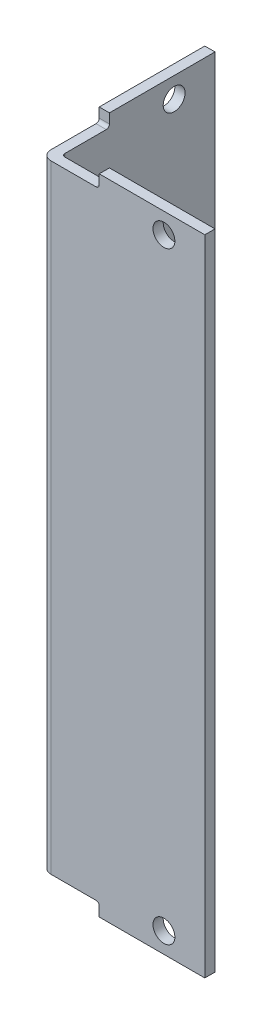
SolidWorks part; units mm, degrees
material "6061-T6 (SS)"
ref_plane "Front Plane" through (0, 0, 0) normal (0, 0, 1) x (1, 0, 0)
ref_plane "Top Plane" through (0, 0, 0) normal (0, 1, 0) x (1, 0, 0)
ref_plane "Right Plane" through (0, 0, 0) normal (1, 0, 0) x (0, 0, -1)
sketch "Sketch1" plane through (0, 0, 0) normal (0, 1, 0) x (1, 0, 0)
  line L1 (-12.7, -12.7) -> (12.7, -12.7)
  line L2 (-12.7, -12.7) -> (-12.7, 12.7)
  line L3 (-12.7, 12.7) -> (12.7, 12.7)
  line L4 (12.7, -12.7) -> (12.7, 12.7)
  line L5 (-12.7, -12.7) -> (12.7, 12.7) construction
  line L6 (-12.7, 12.7) -> (12.7, -12.7) construction
  point P0 (0, 0)
  dimension "D1" = 25.4
  dimension "D2" = 25.4
extrude "Boss-Extrude1" add sketch "Sketch1" along normal mid plane 113.5
sketch "Sketch2" plane through (0, 56.75, 0) normal (0, 1, 0) x (1, 0, 0)
  line L0 (-12.7, 12.7) -> (-12.7, -12.7) construction
  line L1 (12.7, 12.7) -> (-11.1125, 12.7)
  line L2 (12.7, 12.7) -> (12.7, -11.1125)
  line L3 (12.7, -11.1125) -> (-11.1125, -11.1125)
  line L4 (-11.1125, 12.7) -> (-11.1125, -11.1125)
  line L5 (-12.7, -12.7) -> (12.7, -12.7) construction
  dimension "D1" = 1.5875
  dimension "D2" = 1.5875
extrude "Cut-Extrude1" cut sketch "Sketch2" against normal through all
fillet "Fillet1" radius 0.508 1 edges at (-11.1125, 0, 11.1125)
hole_wizard "M3 Clearance Hole1" positions "Sketch3" profile "Sketch4" hole size "M3" standard "ANSI Metric" end condition through all
sketch "Sketch3" plane through (0, 0, 12.7) normal (0, 0, 1) x (1, 0, 0)
  line L1 (-12.7, 56.75) -> (12.7, 56.75) construction
  line L2 (12.7, 56.75) -> (12.7, -56.75) construction
  point P0 (6.35, 47.075)
  dimension "D1" = 6.35
  dimension "D2" = 9.675
sketch "Sketch4" plane through (6.35, 47.075, 12.7) normal (1, 0, 0) x (0, -1, 0)
  line L0 (0, 0) -> (0, 25.4)
  line L1 (0, 25.4) -> (1.7, 25.4)
  line L2 (1.7, 25.4) -> (1.7, 0)
  line L5 (1.7, 0) -> (0, 0)
  line L11 (0, -6.35) -> (0, 107.95) construction
  dimension "Thru Hole Dia." = 3.4
  dimension "Thru Hole Depth" = 25.4
hole_wizard "M3 Clearance Hole2" positions "Sketch5" profile "Sketch6" hole size "M3" standard "ANSI Metric" end condition through all
sketch "Sketch5" plane through (-12.7, 0, 0) normal (-1, 0, 0) x (0, 0, 1)
  line L1 (-12.7, 56.75) -> (12.7, 56.75) construction
  line L2 (-12.7, 56.75) -> (-12.7, -56.75) construction
  point P0 (-6.35, 47.075)
  dimension "D1" = 6.35
  dimension "D2" = 9.675
sketch "Sketch6" plane through (-12.7, 47.075, -6.35) normal (0, 1, 0) x (0, 0, 1)
  line L0 (0, 0) -> (0, 25.4)
  line L1 (0, 25.4) -> (1.7, 25.4)
  line L2 (1.7, 25.4) -> (1.7, 0)
  line L5 (1.7, 0) -> (0, 0)
  line L11 (0, -6.35) -> (0, 107.95) construction
  dimension "Thru Hole Dia." = 3.4
  dimension "Thru Hole Depth" = 25.4
hole_wizard "M3 Clearance Hole3" positions "Sketch7" profile "Sketch8" hole size "M3" standard "ANSI Metric" end condition through all
sketch "Sketch7" plane through (0, 0, 12.7) normal (0, 0, 1) x (1, 0, 0)
  line L2 (-12.7, -56.75) -> (12.7, -56.75) construction
  line L3 (12.7, 56.75) -> (12.7, -56.75) construction
  point P0 (6.35, -46.575)
  dimension "D1" = 6.35
  dimension "D2" = 10.175
sketch "Sketch8" plane through (6.35, -46.575, 12.7) normal (1, 0, 0) x (0, -1, 0)
  line L0 (0, 0) -> (0, 25.4)
  line L1 (0, 25.4) -> (1.7, 25.4)
  line L2 (1.7, 25.4) -> (1.7, 0)
  line L5 (1.7, 0) -> (0, 0)
  line L11 (0, -6.35) -> (0, 107.95) construction
  dimension "Thru Hole Dia." = 3.4
  dimension "Thru Hole Depth" = 25.4
hole_wizard "M3 Clearance Hole4" positions "Sketch9" profile "Sketch10" hole size "M3" standard "ANSI Metric" end condition through all
sketch "Sketch9" plane through (-12.7, 0, 0) normal (-1, 0, 0) x (0, 0, 1)
  line L1 (-12.7, -56.75) -> (12.7, -56.75) construction
  line L2 (-12.7, 56.75) -> (-12.7, -56.75) construction
  point P0 (-6.35, -46.575)
  dimension "D1" = 6.35
  dimension "D2" = 10.175
sketch "Sketch10" plane through (-12.7, -46.575, -6.35) normal (0, 1, 0) x (0, 0, 1)
  line L0 (0, 0) -> (0, 25.4)
  line L1 (0, 25.4) -> (1.7, 25.4)
  line L2 (1.7, 25.4) -> (1.7, 0)
  line L5 (1.7, 0) -> (0, 0)
  line L11 (0, -6.35) -> (0, 107.95) construction
  dimension "Thru Hole Dia." = 3.4
  dimension "Thru Hole Depth" = 25.4
fillet "Fillet2" radius 1.5 1 edges at (-12.7, 0, 12.7)
sketch "Sketch11" plane through (-12.7, 0, 0) normal (-1, 0, 0) x (0, 0, 1)
  line L0 (12.7, 56.75) -> (12.7, -56.75) construction
  line L1 (-12.7, 56.75) -> (4.2, 56.75)
  line L2 (-12.7, 56.75) -> (-12.7, 50.25)
  line L3 (-12.7, 50.25) -> (4.2, 50.25)
  line L4 (4.2, 56.75) -> (4.2, 50.25)
  line L6 (-12.7, -56.75) -> (4.2, -56.75)
  line L7 (-12.7, -56.75) -> (-12.7, -49.75)
  line L8 (-12.7, -49.75) -> (4.2, -49.75)
  line L9 (4.2, -56.75) -> (4.2, -49.75)
  dimension "D1" = 8.5
  dimension "D2" = 6.5
  dimension "D3" = 7
extrude "Cut-Extrude2" cut sketch "Sketch11" against normal up to next
sketch "Sketch12" plane through (0, 0, 12.7) normal (0, 0, 1) x (1, 0, 0)
  line L0 (-12.7, -56.75) -> (-12.7, 56.75) construction
  line L1 (12.7, 56.75) -> (-4.2, 56.75)
  line L2 (12.7, 56.75) -> (12.7, 50.25)
  line L3 (12.7, 50.25) -> (-4.2, 50.25)
  line L4 (-4.2, 56.75) -> (-4.2, 50.25)
  line L5 (12.7, -56.75) -> (-4.2, -56.75)
  line L6 (12.7, -56.75) -> (12.7, -49.75)
  line L7 (12.7, -49.75) -> (-4.2, -49.75)
  line L8 (-4.2, -56.75) -> (-4.2, -49.75)
  dimension "D1" = 8.5
  dimension "D2" = 7
  dimension "D3" = 8.5
  dimension "D4" = 6.5
extrude "Cut-Extrude3" cut sketch "Sketch12" against normal up to next
fillet "Fillet3" radius 3.81 4 edges at (-4.2, -49.75, 11.9062) (-11.9063, -49.75, 4.2) (-11.9063, 50.25, 4.2) (-4.2, 50.25, 11.9062)
sketch "Sketch13" plane through (-12.7, 0, 0) normal (-1, 0, 0) x (0, 0, 1)
  line L0 (4.2, -56.75) -> (4.2, 56.75) construction
  line L9 (2.7, -56.75) -> (2.7, 56.75) construction
  line L10 (-12.7, 50.25) -> (-12.7, -49.75) construction
  line L11 (2.7, -43.4) -> (-12.7, -43.4)
  line L12 (2.7, -43.4) -> (2.7, 43.9)
  line L13 (2.7, 43.9) -> (-12.7, 43.9)
  line L14 (-12.7, -43.4) -> (-12.7, 43.9)
  circle A2 centre (-6.35, 47.075) radius 1.7 construction
  circle A3 centre (-6.35, -46.575) radius 1.7 construction
  dimension "D2" = 3.175
  dimension "D3" = 3.175
  dimension "D1" = 1.5
extrude "Cut-Extrude4" cut sketch "Sketch13" against normal up to next
sketch "Sketch14" plane through (0, 0, 12.7) normal (0, 0, 1) x (1, 0, 0)
  line L0 (-4.2, 56.75) -> (-4.2, -56.75) construction
  line L1 (-2.7, 56.75) -> (-2.7, -56.75) construction
  line L2 (12.7, 50.25) -> (12.7, -49.75) construction
  line L3 (-2.7, -43.4) -> (12.7, -43.4)
  line L4 (-2.7, -43.4) -> (-2.7, 43.9)
  line L5 (-2.7, 43.9) -> (12.7, 43.9)
  line L6 (12.7, -43.4) -> (12.7, 43.9)
  circle A0 centre (6.35, 47.075) radius 1.7 construction
  circle A1 centre (6.35, -46.575) radius 1.7 construction
  dimension "D2" = 3.175
  dimension "D3" = 3.175
  dimension "D1" = 1.5
extrude "Cut-Extrude5" cut sketch "Sketch14" against normal up to next
chamfer "Chamfer2" distance 6.35 angle 45 4 edges at (-11.9063, 43.9, 2.7) (-2.7, 43.9, 11.9062) (-2.7, -43.4, 11.9062) (-11.9062, -43.4, 2.7)
fillet "Fillet5" radius 3.81 8 edges at (3.65, -43.4, 11.9062) (-2.7, -37.05, 11.9062) (-11.9063, -43.4, -3.65) (-11.9063, -37.05, 2.7) (-11.9063, 43.9, -3.65) (-11.9063, 37.55, 2.7) (-2.7, 37.55, 11.9062) (3.65, 43.9, 11.9062)
sketch "Sketch15" plane through (0, 56.75, 0) normal (0, 1, 0) x (1, 0, 0)
  line L0 (-11.2, -12.7) -> (-4.2, -12.7) construction
  line L1 (-12.7, -12.7) -> (-0.39, -12.7)
  line L2 (-12.7, -12.7) -> (-12.7, -0.39)
  line L3 (-12.7, -0.39) -> (-0.39, -0.39)
  line L4 (-0.39, -12.7) -> (-0.39, -0.39)
  line L5 (-12.7, -4.2) -> (-12.7, -11.2) construction
  line L6 (-0.39, -11.1125) -> (-0.39, -12.7) construction
extrude "Cut-Extrude6" cut sketch "Sketch15" against normal up to surface (6.5 mm away) up to face at (6.155, 50.25, 11.9062)
sketch "Sketch16" plane through (0, 50.25, 0) normal (0, 1, 0) x (1, 0, 0)
  line L0 (-11.2, -12.7) -> (12.7, -12.7) construction
  line L1 (-12.7, -12.7) -> (-5.7, -12.7)
  line L2 (-12.7, -12.7) -> (-12.7, -5.7)
  line L3 (-12.7, -5.7) -> (-5.7, -5.7)
  line L4 (-5.7, -12.7) -> (-5.7, -5.7)
  line L5 (-12.7, 12.7) -> (-12.7, -11.2) construction
  dimension "D1" = 7
  dimension "D2" = 7
sketch "Sketch17" plane through (0, -56.75, 0) normal (0, -1, 0) x (1, 0, 0)
  line L0 (-11.2, 12.7) -> (-4.2, 12.7) construction
  line L1 (-12.7, 12.7) -> (-0.39, 12.7)
  line L2 (-12.7, 12.7) -> (-12.7, 0.39)
  line L3 (-12.7, 0.39) -> (-0.39, 0.39)
  line L4 (-0.39, 12.7) -> (-0.39, 0.39)
  line L5 (-12.7, 4.2) -> (-12.7, 11.2) construction
  line L6 (-11.1125, 0.39) -> (-12.7, 0.39) construction
  line L7 (-0.39, 12.7) -> (-0.39, 11.1125) construction
extrude "Cut-Extrude8" cut sketch "Sketch17" against normal up to surface (7 mm away) up to face at (6.155, -49.75, 11.9062)
sketch "Sketch18" plane through (-12.7, 0, 0) normal (-1, 0, 0) x (0, 0, 1)
  line L0 (-12.7, -43.4) -> (-5.2282, -43.4) construction
  line L1 (5.7, -43.4) -> (11.2, -43.4)
  line L2 (5.7, -43.4) -> (5.7, -40.4)
  line L3 (5.7, -40.4) -> (11.2, -40.4)
  line L4 (11.2, -43.4) -> (11.2, -40.4)
  line L5 (12.7, 50.25) -> (12.7, -49.75) construction
  point P8 (8.45, -40.4)
  dimension "D1" = 5.5
  dimension "D2" = 3
  dimension "D3" = 4.25
sketch "Sketch19" plane through (0, -49.75, 0) normal (0, -1, 0) x (1, 0, 0)
  line L0 (12.7, 12.7) -> (-11.2, 12.7) construction
  line L1 (-12.7, 5.7) -> (-5.7, 5.7)
  line L2 (-12.7, 5.7) -> (-12.7, 12.7)
  line L3 (-12.7, 12.7) -> (-5.7, 12.7)
  line L4 (-5.7, 5.7) -> (-5.7, 12.7)
  line L5 (-12.7, 11.2) -> (-12.7, -12.7) construction
sketch "Sketch20" plane through (-12.7, 0, 0) normal (-1, 0, 0) x (0, 0, 1)
  line L0 (-12.7, 43.9) -> (-12.7, -43.4)
  line L14 (11.2, -49.75) -> (11.2, 50.25)
  line L15 (11.2, 50.25) -> (-12.7, 50.25)
  line L16 (-12.7, 50.25) -> (-12.7, 43.9)
  line L17 (-12.7, 43.9) -> (-5.2282, 43.9)
  line L18 (-2.5341, 42.7841) -> (1.5841, 38.6659)
  line L19 (2.7, 35.9718) -> (2.7, -35.4718)
  line L20 (1.5841, -38.1659) -> (-2.5341, -42.2841)
  line L21 (-5.2282, -43.4) -> (-12.7, -43.4)
  line L22 (-12.7, -43.4) -> (-12.7, -49.75)
  line L23 (-12.7, -49.75) -> (11.2, -49.75)
  line L27 (11.2, -49.75) -> (11.2, 50.25)
  line L28 (11.2, 50.25) -> (-12.7, 50.25)
  line L29 (-12.7, 50.25) -> (-12.7, 43.9)
  line L30 (-12.7, 43.9) -> (-5.2282, 43.9)
  line L31 (-2.5341, 42.7841) -> (1.5841, 38.6659)
  line L32 (2.7, 35.9718) -> (2.7, -35.4718)
  line L33 (1.5841, -38.1659) -> (-2.5341, -42.2841)
  line L34 (-5.2282, -43.4) -> (-12.7, -43.4)
  line L35 (-12.7, -43.4) -> (-12.7, -49.75)
  line L36 (-12.7, -49.75) -> (11.2, -49.75)
  arc A6 (-2.5341, 42.7841) -> (-5.2282, 43.9) centre (-5.2282, 40.09) ccw
  arc A7 (2.7, 35.9718) -> (1.5841, 38.6659) centre (-1.11, 35.9718) ccw
  arc A8 (1.5841, -38.1659) -> (2.7, -35.4718) centre (-1.11, -35.4718) ccw
  arc A9 (-5.2282, -43.4) -> (-2.5341, -42.2841) centre (-5.2282, -39.59) ccw
  arc A11 (-2.5341, 42.7841) -> (-5.2282, 43.9) centre (-5.2282, 40.09) ccw
  arc A12 (2.7, 35.9718) -> (1.5841, 38.6659) centre (-1.11, 35.9718) ccw
  arc A13 (1.5841, -38.1659) -> (2.7, -35.4718) centre (-1.11, -35.4718) ccw
  arc A14 (-5.2282, -43.4) -> (-2.5341, -42.2841) centre (-5.2282, -39.59) ccw
  line M26 (-12.7, 43.9) -> (-5.2282, 43.9)
  arc M27 (-5.2282, 43.9) -> (-2.5341, 42.7841) centre (-5.2282, 40.09) cw
  line M28 (-2.5341, 42.7841) -> (1.5841, 38.6659)
  arc M29 (1.5841, 38.6659) -> (2.7, 35.9718) centre (-1.11, 35.9718) cw
  line M30 (2.7, 35.9718) -> (2.7, -35.4718)
  arc M31 (2.7, -35.4718) -> (1.5841, -38.1659) centre (-1.11, -35.4718) cw
  line M32 (1.5841, -38.1659) -> (-2.5341, -42.2841)
  arc M33 (-2.5341, -42.2841) -> (-5.2282, -43.4) centre (-5.2282, -39.59) cw
  line M34 (-5.2282, -43.4) -> (-12.7, -43.4)
  dimension "D1" = 0
extrude "Boss-Extrude2" add sketch "Sketch20" against normal up to surface (1.5875 mm away) contours L0 M26 M34 M33 M32 M31 M30 M29 M28 M27 region at (-12.7, 0.25, -5.177) up to face at (-11.1125, -46.575, -4.65)
sketch "Sketch21" plane through (0, 0, 12.7) normal (0, 0, 1) x (1, 0, 0)
  line L0 (12.7, 43.9) -> (12.7, -43.4)
  line L14 (-11.2, 50.25) -> (-11.2, -49.75)
  line L15 (-11.2, -49.75) -> (12.7, -49.75)
  line L16 (12.7, -49.75) -> (12.7, -43.4)
  line L17 (12.7, -43.4) -> (5.2282, -43.4)
  line L18 (2.5341, -42.2841) -> (-1.5841, -38.1659)
  line L19 (-2.7, -35.4718) -> (-2.7, 35.9718)
  line L20 (-1.5841, 38.6659) -> (2.5341, 42.7841)
  line L21 (5.2282, 43.9) -> (12.7, 43.9)
  line L22 (12.7, 43.9) -> (12.7, 50.25)
  line L23 (12.7, 50.25) -> (-11.2, 50.25)
  line L27 (-11.2, 50.25) -> (-11.2, -49.75)
  line L28 (-11.2, -49.75) -> (12.7, -49.75)
  line L29 (12.7, -49.75) -> (12.7, -43.4)
  line L30 (12.7, -43.4) -> (5.2282, -43.4)
  line L31 (2.5341, -42.2841) -> (-1.5841, -38.1659)
  line L32 (-2.7, -35.4718) -> (-2.7, 35.9718)
  line L33 (-1.5841, 38.6659) -> (2.5341, 42.7841)
  line L34 (5.2282, 43.9) -> (12.7, 43.9)
  line L35 (12.7, 43.9) -> (12.7, 50.25)
  line L36 (12.7, 50.25) -> (-11.2, 50.25)
  arc A6 (2.5341, -42.2841) -> (5.2282, -43.4) centre (5.2282, -39.59) ccw
  arc A7 (-2.7, -35.4718) -> (-1.5841, -38.1659) centre (1.11, -35.4718) ccw
  arc A8 (-1.5841, 38.6659) -> (-2.7, 35.9718) centre (1.11, 35.9718) ccw
  arc A9 (5.2282, 43.9) -> (2.5341, 42.7841) centre (5.2282, 40.09) ccw
  arc A11 (2.5341, -42.2841) -> (5.2282, -43.4) centre (5.2282, -39.59) ccw
  arc A12 (-2.7, -35.4718) -> (-1.5841, -38.1659) centre (1.11, -35.4718) ccw
  arc A13 (-1.5841, 38.6659) -> (-2.7, 35.9718) centre (1.11, 35.9718) ccw
  arc A14 (5.2282, 43.9) -> (2.5341, 42.7841) centre (5.2282, 40.09) ccw
  line M24 (12.7, -43.4) -> (5.2282, -43.4)
  arc M25 (5.2282, -43.4) -> (2.5341, -42.2841) centre (5.2282, -39.59) cw
  line M26 (2.5341, -42.2841) -> (-1.5841, -38.1659)
  arc M27 (-1.5841, -38.1659) -> (-2.7, -35.4718) centre (1.11, -35.4718) cw
  line M28 (-2.7, -35.4718) -> (-2.7, 35.9718)
  arc M29 (-2.7, 35.9718) -> (-1.5841, 38.6659) centre (1.11, 35.9718) cw
  line M30 (-1.5841, 38.6659) -> (2.5341, 42.7841)
  arc M31 (2.5341, 42.7841) -> (5.2282, 43.9) centre (5.2282, 40.09) cw
  line M32 (5.2282, 43.9) -> (12.7, 43.9)
  dimension "D1" = 0
extrude "Boss-Extrude3" add sketch "Sketch21" against normal up to surface (1.5875 mm away) contours L0 M32 M31 M30 M29 M28 M27 M26 M25 M24 region at (5.177, 0.25, 12.7) up to face at (8.05, -46.575, 11.1125)
sketch "Sketch23" plane through (-11.1125, 0, 0) normal (1, 0, 0) x (0, 0, -1)
  line L0 (-220.6296, -34.1208) -> (-227.7171, -34.1208)
  line L1 (-220.6296, -34.1208) -> (-220.6296, -41.1208)
  line L2 (-220.6296, -41.1208) -> (-227.7171, -41.1208)
  line L3 (-227.7171, -34.1208) -> (-227.7171, -41.1208)
  line L4 (-11.1125, -49.75) -> (-11.1125, 50.25) construction
  line L5 (-9.1125, 43.25) -> (-2.6125, 43.25)
  line L6 (-9.1125, 43.25) -> (-9.1125, 36.25)
  line L7 (-9.1125, 36.25) -> (-2.6125, 36.25)
  line L8 (-2.6125, 43.25) -> (-2.6125, 36.25)
  line L9 (-10.6045, 50.25) -> (12.7, 50.25) construction
  dimension "D1" = 8.5
  dimension "D2" = 2
  dimension "D3" = 7
  dimension "D4" = 14
extrude "Cut-Extrude12" cut sketch "Sketch23" against normal up to next contours L8 L7 L6 L5
fillet "Fillet9" radius 1.5875 4 edges at (-11.9063, 36.25, 2.6125) (-11.9063, 43.25, 2.6125) (-11.9062, 43.25, 9.1125) (-11.9062, 36.25, 9.1125)
ref_plane "Plane1" through (0, 0.25, 0) normal (0, 1, 0) x (1, 0, 0)
mirror "Mirror3" about plane through (0, 0.25, 0) normal (0, 1, 0) of "Fillet9", "Cut-Extrude12"
sketch "Sketch24" plane through (-12.7, 0, 0) normal (-1, 0, 0) x (0, 0, 1)
  line L0 (4.2, 36.25) -> (7.525, 36.25) construction
  line L1 (2.6125, 37.8375) -> (2.6125, 41.6625) construction
  line L2 (4.2, 43.25) -> (7.525, 43.25) construction
  line L3 (9.1125, 37.8375) -> (9.1125, 41.6625) construction
  line L4 (4.2, 36.25) -> (7.525, 36.25)
  line L5 (2.6125, 37.8375) -> (2.6125, 41.6625)
  line L6 (4.2, 43.25) -> (7.525, 43.25)
  line L7 (9.1125, 37.8375) -> (9.1125, 41.6625)
  arc A0 (2.6125, 37.8375) -> (4.2, 36.25) centre (4.2, 37.8375) ccw construction
  arc A1 (4.2, 43.25) -> (2.6125, 41.6625) centre (4.2, 41.6625) ccw construction
  arc A2 (9.1125, 41.6625) -> (7.525, 43.25) centre (7.525, 41.6625) ccw construction
  arc A3 (7.525, 36.25) -> (9.1125, 37.8375) centre (7.525, 37.8375) ccw construction
  arc A4 (2.6125, 37.8375) -> (4.2, 36.25) centre (4.2, 37.8375) ccw
  arc A5 (4.2, 43.25) -> (2.6125, 41.6625) centre (4.2, 41.6625) ccw
  arc A6 (9.1125, 41.6625) -> (7.525, 43.25) centre (7.525, 41.6625) ccw
  arc A7 (7.525, 36.25) -> (9.1125, 37.8375) centre (7.525, 37.8375) ccw
extrude "Boss-Extrude4" add sketch "Sketch24" against normal up to surface (1.5875 mm away) up to face at (-11.1125, -39.25, 5.8625)
sketch "Sketch25" plane through (0, -49.75, 0) normal (0, -1, 0) x (1, 0, 0)
  line L0 (12.7, 12.7) -> (-11.2, 12.7) construction
  line L1 (-12.7, 11.2) -> (-12.7, -12.7) construction
  line L2 (12.7, 12.7) -> (-11.2, 12.7) construction
  line L3 (-12.7, 11.2) -> (-12.7, -12.7) construction
  line L4 (-12.7, 5.7) -> (-12.7, 12.7) construction
  line L5 (-12.7, 12.7) -> (-3.7, 12.7)
  line L6 (-12.7, 12.7) -> (-12.7, 3.7)
  line L7 (-12.7, 3.7) -> (-3.7, 3.7)
  line L8 (-3.7, 12.7) -> (-3.7, 3.7)
  dimension "D1" = 9
  dimension "D2" = 9
extrude "Cut-Extrude13" cut sketch "Sketch25" against normal blind 2
fillet "Fillet10" radius 0.5 2 edges at (-11.9062, -47.75, 3.7) (-3.7, -47.75, 11.9062)
mirror "Mirror4" about plane through (0, 0.25, 0) normal (0, 1, 0) of "Cut-Extrude13", "Fillet10"
